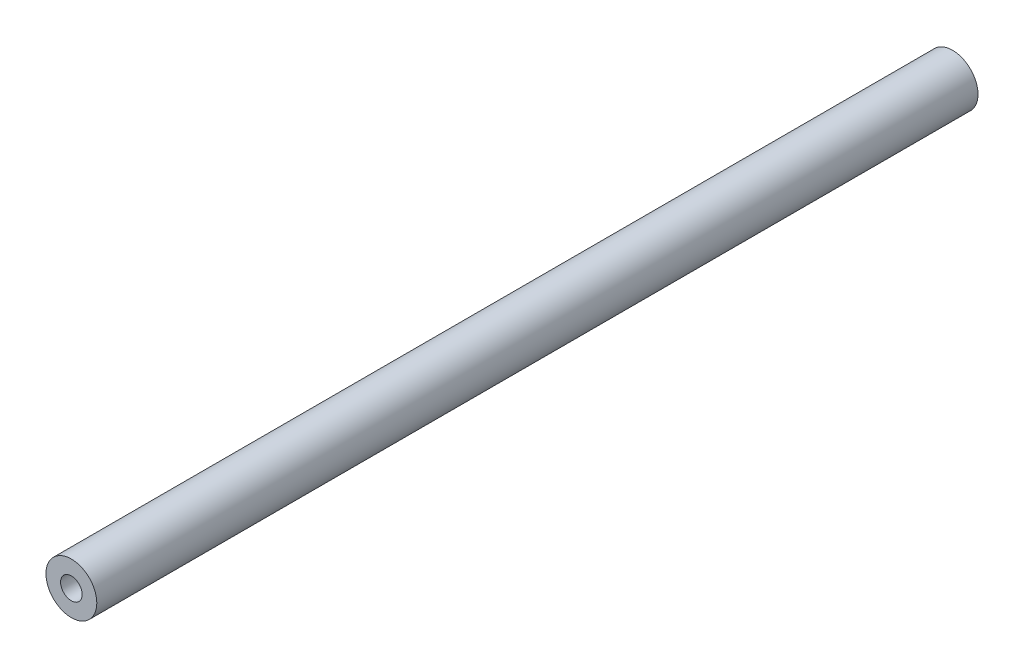
SolidWorks part; units mm, degrees
material "7075-T6, Plate (SS)"
ref_plane "Front Plane" through (0, 0, 0) normal (0, 0, 1) x (1, 0, 0)
ref_plane "Top Plane" through (0, 0, 0) normal (0, 1, 0) x (1, 0, 0)
ref_plane "Right Plane" through (0, 0, 0) normal (1, 0, 0) x (0, 0, -1)
sketch "Sketch1" plane through (0, 0, 0) normal (0, 0, 1) x (1, 0, 0)
  circle A1 centre (0, 0) radius 4.7625
  dimension "D1" = 9.525
extrude "Boss-Extrude1" add sketch "Sketch1" against normal blind 165.1
sketch "Sketch5" plane through (0, 0, -165.1) normal (0, 0, -1) x (-1, 0, 0)
  point P0 (0, 0)
hole_wizard "#10-32 Tapped Hole1" positions "Sketch5" profile "Sketch6" tap size "#10-32" standard "ANSI Inch"
sketch "Sketch6" plane through (0, 0, -165.1) normal (1, 0, 0) x (0, 1, 0)
  line L0 (0, 0) -> (0, 20.2633)
  line L1 (0, 20.2633) -> (2.0193, 19.05)
  line L2 (2.0193, 19.05) -> (2.0193, 0)
  line L5 (2.0193, 0) -> (0, 0)
  line L10 (0, 20.2633) -> (-2.0193, 19.05) construction
  line L11 (0, -6.35) -> (0, 107.95) construction
  dimension "Tap Drill Dia." = 4.0386
  dimension "Tap Drill Depth" = 19.05
  dimension "Drill Angle" = 118
cosmetic thread "Hole Thread1"
hole_wizard "#10-32 Tapped Hole4" positions "Sketch11" profile "Sketch12" tap size "#10-32" standard "ANSI Inch"
sketch "Sketch11" plane through (0, 0, 0) normal (0, 0, 1) x (1, 0, 0)
  point P0 (0, 0)
sketch "Sketch12" plane through (0, 0, 0) normal (1, 0, 0) x (0, -1, 0)
  line L0 (0, 0) -> (0, 20.2633)
  line L1 (0, 20.2633) -> (2.0193, 19.05)
  line L2 (2.0193, 19.05) -> (2.0193, 0)
  line L5 (2.0193, 0) -> (0, 0)
  line L10 (0, 20.2633) -> (-2.0193, 19.05) construction
  line L11 (0, -6.35) -> (0, 107.95) construction
  dimension "Tap Drill Dia." = 4.0386
  dimension "Tap Drill Depth" = 19.05
  dimension "Drill Angle" = 118
cosmetic thread "Hole Thread4"
